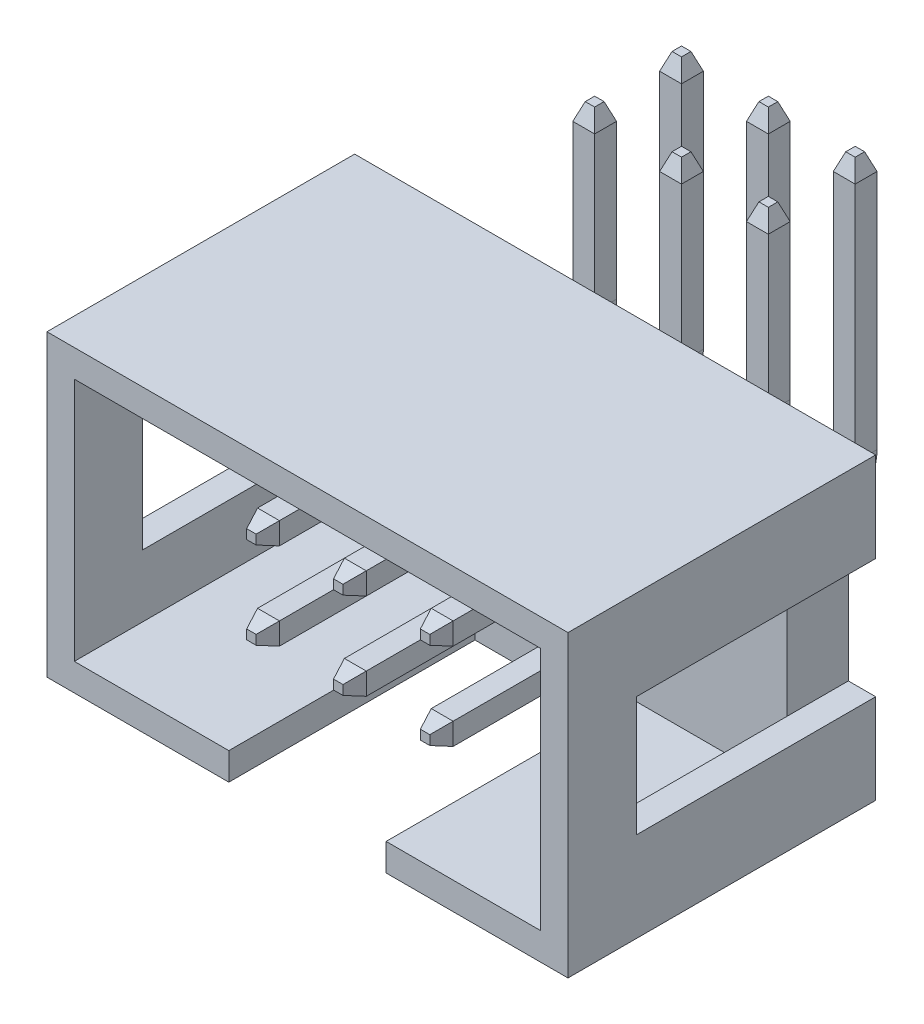
SolidWorks part; units mm, degrees
ref_plane "Спереди" through (0, 0, 0) normal (0, 0, 1) x (1, 0, 0)
ref_plane "Сверху" through (0, 0, 0) normal (0, 1, 0) x (1, 0, 0)
ref_plane "Справа" through (0, 0, 0) normal (1, 0, 0) x (0, 0, -1)
sketch "Эскиз1" plane through (0, 0, 0) normal (0, 0, 1) x (1, 0, 0)
  line L1 (-7.62, -4.375) -> (7.62, -4.375)
  line L2 (-7.62, -4.375) -> (-7.62, 4.375)
  line L3 (-7.62, 4.375) -> (7.62, 4.375)
  line L4 (7.62, -4.375) -> (7.62, 4.375)
  point P4 (0, 4.375)
  point P6 (-7.62, 0)
  dimension "D1" = 8.75
  dimension "D2" = 15.24
extrude "Бобышка-Вытянуть1" add sketch "Эскиз1" along normal blind 1.8
sketch "Эскиз2" plane through (0, 0, 1.8) normal (0, 0, 1) x (1, 0, 0)
  line L1 (-7.62, 4.375) -> (7.62, 4.375)
  line L2 (-7.62, 4.375) -> (-7.62, -4.375)
  line L3 (-7.62, -4.375) -> (7.62, -4.375)
  line L4 (7.62, 4.375) -> (7.62, -4.375)
  line L5 (-6.82, 3.575) -> (6.82, 3.575)
  line L6 (-6.82, 3.575) -> (-6.82, -3.575)
  line L7 (-6.82, -3.575) -> (6.82, -3.575)
  line L8 (6.82, 3.575) -> (6.82, -3.575)
  dimension "D1" = 0.8
  dimension "D2" = 0.8
  dimension "D3" = 0.8
  dimension "D4" = 0.8
extrude "Бобышка-Вытянуть2" add sketch "Эскиз2" along normal offset from surface (7.2 mm away) 9 up to face at (0, 0, 0)
sketch "Эскиз3" plane through (0, 0, 1.8) normal (0, 0, 1) x (1, 0, 0)
  line L0 (-7.62, 4.375) -> (-7.62, -4.375) construction
  line L1 (6.82, 1.75) -> (7.62, 1.75)
  line L2 (6.82, 1.75) -> (6.82, -1.75)
  line L3 (6.82, -1.75) -> (7.62, -1.75)
  line L4 (7.62, 1.75) -> (7.62, -1.75)
  line L5 (6.82, 1.75) -> (7.62, -1.75) construction
  line L6 (6.82, -1.75) -> (7.62, 1.75) construction
  line L7 (-6.82, 1.75) -> (-7.62, 1.75)
  line L8 (-6.82, 1.75) -> (-6.82, -1.75)
  line L9 (-6.82, -1.75) -> (-7.62, -1.75)
  line L10 (-7.62, 1.75) -> (-7.62, -1.75)
  line L11 (-6.82, 1.75) -> (-7.62, -1.75) construction
  line L12 (-6.82, -1.75) -> (-7.62, 1.75) construction
  line L13 (-6.82, 3.575) -> (-6.82, -3.575) construction
  line L14 (7.62, -4.375) -> (7.62, 4.375) construction
  line L16 (6.82, -3.575) -> (6.82, 3.575) construction
  point P0 (7.22, 0)
  point P5 (-7.22, 0)
  point P16 (0, 0)
  point P17 (7.22, 0)
  dimension "D1" = 3.5
extrude "Вырез-Вытянуть1" cut sketch "Эскиз3" against normal up to surface (1.8 mm away) and the other way offset from surface 2 up to face at (0, 0, 0) other way up to face at (0, 0, 9)
sketch "Эскиз4" plane through (0, 0, 9) normal (0, 0, 1) x (1, 0, 0)
  line L0 (6.82, -3.575) -> (-6.82, -3.575) construction
  line L1 (-2.3, -4.375) -> (2.3, -4.375)
  line L2 (-2.3, -4.375) -> (-2.3, -3.575)
  line L3 (-2.3, -3.575) -> (2.3, -3.575)
  line L4 (2.3, -4.375) -> (2.3, -3.575)
  line L5 (-2.3, -4.375) -> (2.3, -3.575) construction
  line L6 (-2.3, -3.575) -> (2.3, -4.375) construction
  line L7 (7.62, -4.375) -> (-7.62, -4.375) construction
  point P0 (0, -3.975)
  point P9 (0, 0)
  point P10 (0, 0)
  dimension "D1" = 4.6
extrude "Вырез-Вытянуть2" cut sketch "Эскиз4" against normal up to surface (7.2 mm away) up to face at (0, 0, 1.8)
sketch "Эскиз5" plane through (0, 0, 1.8) normal (0, 0, 1) x (1, 0, 0)
  line L0 (-2.54, 1.27) -> (2.54, 1.27) construction
  line L1 (2.54, 1.27) -> (2.54, -1.27) construction
  line L2 (2.54, -1.27) -> (-2.54, -1.27) construction
  line L3 (-2.54, -1.27) -> (-2.54, 1.27) construction
  line L5 (0, -1.27) -> (0, 1.27) construction
  line L6 (-0.32, 0.95) -> (0.32, 0.95)
  line L7 (-0.32, 0.95) -> (-0.32, 1.59)
  line L8 (-0.32, 1.59) -> (0.32, 1.59)
  line L9 (0.32, 0.95) -> (0.32, 1.59)
  line L10 (-0.32, 0.95) -> (0.32, 1.59) construction
  line L11 (-0.32, 1.59) -> (0.32, 0.95) construction
  point P11 (0, 1.27)
  point P12 (-0.1946, 1.4538)
  dimension "D1" = 2.54
  dimension "D2" = 2.54
  dimension "D3" = 0.64
sketch "Эскиз6" plane through (0, -4.375, 0) normal (0, -1, 0) x (1, 0, 0)
  line L0 (-4.9764, 5.1897) -> (-3.1846, 5.1897)
  line L1 (-3.1846, 5.1897) -> (-4.0805, 3.7162)
  line L2 (-4.0805, 3.7162) -> (-4.9764, 5.1897)
extrude "Вырез-Вытянуть3" cut sketch "Эскиз6" against normal blind 0.1
sketch "Эскиз8" plane through (0, 0, 0) normal (0, 0, 1) x (1, 0, 0)
  line L0 (-2.54, 1.27) -> (2.54, 1.27) construction
  line L1 (2.54, 1.27) -> (2.54, -1.27) construction
  line L2 (2.54, -1.27) -> (-2.54, -1.27) construction
  line L3 (-2.54, -1.27) -> (-2.54, 1.27) construction
  line L5 (0, -1.27) -> (0, 1.27) construction
  line L6 (-0.32, -1.59) -> (0.32, -1.59)
  line L7 (-0.32, -1.59) -> (-0.32, -0.95)
  line L8 (-0.32, -0.95) -> (0.32, -0.95)
  line L9 (0.32, -1.59) -> (0.32, -0.95)
  line L10 (-0.32, -1.59) -> (0.32, -0.95) construction
  line L11 (-0.32, -0.95) -> (0.32, -1.59) construction
  point P7 (0, 0)
  point P11 (0, -1.27)
  point P12 (-0.1946, 1.4538)
  point P13 (0, 0)
  dimension "D1" = 2.54
  dimension "D2" = 2.54
  dimension "D3" = 0.64
  dimension "D4" = 1.27
sketch "Эскиз9" plane through (0, 0, 0) normal (-1, 0, 0) x (0, 0, 1)
  line L0 (8.1, -1.27) -> (0, -1.27)
  line L1 (0, -1.27) -> (-3.48, -1.27)
  line L2 (-4.48, -0.27) -> (-4.48, 7.275)
  line L4 (9, 4.375) -> (9, -4.375) construction
  line L5 (9, 4.375) -> (0, 4.375) construction
  arc A0 (-3.48, -1.27) -> (-4.48, -0.27) centre (-3.48, -0.27) cw
  dimension "D3" = 2.9
  dimension "D4" = 1
  dimension "D1" = 0.9
  dimension "D2" = 13.48
sketch "Эскиз7" plane through (0, 0, 0) normal (1, 0, 0) x (0, 0, -1)
  line L0 (-1.8, 1.27) -> (-8.1, 1.27)
  line L1 (-1.8, -1.27) -> (-1.8, 1.27) construction
  line L2 (-1.8, 1.27) -> (0.94, 1.27)
  line L3 (1.94, 2.27) -> (1.94, 7.275)
  line L4 (-9, 4.375) -> (-9, -4.375) construction
  line L6 (4.48, -0.27) -> (4.48, 7.275) construction
  arc A0 (0.94, 1.27) -> (1.94, 2.27) centre (0.94, 2.27) ccw
  point P8 (0, 0)
  point P14 (0, 0)
  dimension "D3" = 1
  dimension "D1" = 0.9
  dimension "D2" = 2.54
sweep "По траектории2" add profiles "Эскиз8" path "Эскиз9"
sweep "По траектории3" add profiles "Эскиз5" path "Эскиз7"
chamfer "Фаска16" distance 0.5 angle 20 4 edges at (0, 7.275, -1.62) (-0.32, 7.275, -1.94) (0, 7.275, -2.26) (0.32, 7.275, -1.94) first distance on face at (0, 4.7725, -1.62) first distance on face at (-0.32, 4.7725, -1.94) first distance on face at (0, 4.7725, -2.26) first distance on face at (0.32, 4.7725, -1.94)
chamfer "Фаска17" distance 0.5 angle 20 4 edges at (0, 7.275, -4.16) (-0.32, 7.275, -4.48) (0, 7.275, -4.8) (0.32, 7.275, -4.48) first distance on face at (0, 3.5025, -4.16) first distance on face at (-0.32, 3.5025, -4.48) first distance on face at (0, 3.5025, -4.8) first distance on face at (0.32, 3.5025, -4.48)
chamfer "Фаска18" distance 0.5 angle 20 4 edges at (0, -1.59, 8.1) (-0.32, -1.27, 8.1) (0, -0.95, 8.1) (0.32, -1.27, 8.1) first distance on face at (0, -1.59, 2.31) first distance on face at (-0.32, -1.27, 2.31) first distance on face at (0, -0.95, 2.31) first distance on face at (0.32, -1.27, 2.31)
chamfer "Фаска19" distance 0.5 angle 20 4 edges at (0, 0.95, 8.1) (-0.32, 1.27, 8.1) (0, 1.59, 8.1) (0.32, 1.27, 8.1) first distance on face at (0, 0.95, 3.58) first distance on face at (-0.32, 1.27, 3.58) first distance on face at (0, 1.59, 3.58) first distance on face at (0.32, 1.27, 3.58)
pattern_linear "Линейный массив2" count 2 spacing 2.54 along (1, 0, 0) of "По траектории2", "По траектории3"
pattern_linear "Линейный массив3" count 2 spacing 2.54 along (-1, 0, 0) of bodies 115 116
equation "\"D3@Эскиз2\"=\"D2@Эскиз2\""
equation "\"D2@Эскиз2\"=\"D1@Эскиз2\""
equation "\"D4@Эскиз2\"=\"D1@Эскиз2\""
